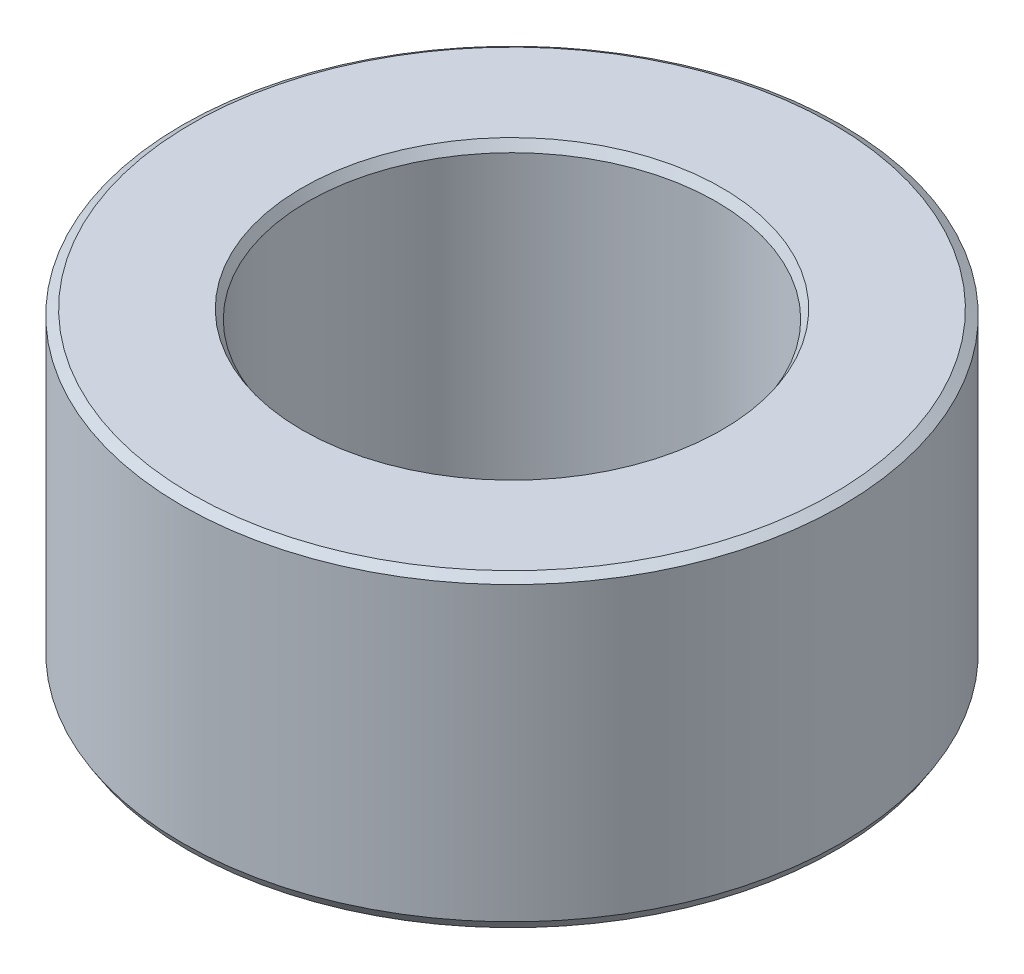
SolidWorks part; units mm, degrees
ref_plane "Front Plane" through (0, 0, 0) normal (0, 0, 1) x (1, 0, 0)
ref_plane "Top Plane" through (0, 0, 0) normal (0, 1, 0) x (1, 0, 0)
ref_plane "Right Plane" through (0, 0, 0) normal (1, 0, 0) x (0, 0, -1)
sketch "Sketch1" plane through (0, 0, 0) normal (0, 1, 0) x (1, 0, 0)
  circle A0 centre (0, 0) radius 50
  dimension "SLEEVE_OD" = 100
extrude "Boss-Extrude1" add sketch "Sketch1" along normal blind 46.5251
sketch "Sketch2" plane through (0, 0, 0) normal (0, 1, 0) x (1, 0, 0)
  circle A0 centre (0, 0) radius 30.9623
  dimension "BORE_D" = 61.9247
extrude "Cut-Extrude1" cut sketch "Sketch2" along normal through all
chamfer "Chamfer1" distance 0.8587 angle 58.084 4 edges at (0, 46.5251, 30.9623) (0, 0, 30.9623) (0, 0, 50) (0, 46.5251, 50) first distance on face at (0, 46.5251, 30.9623) first distance on face at (0, 0, 30.9623) first distance on face at (0, 46.5251, 50)
